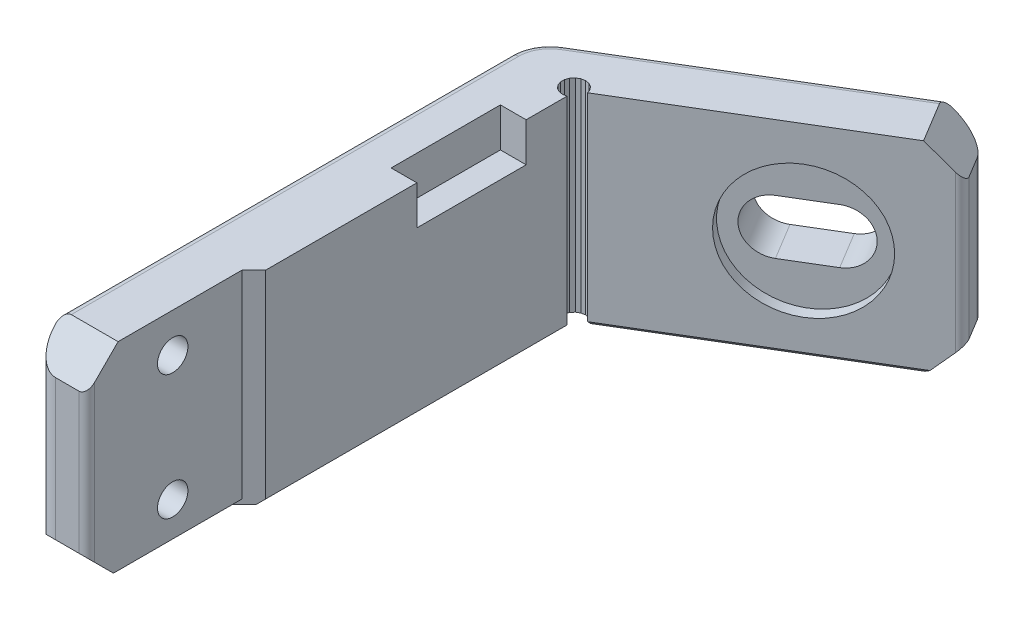
SolidWorks part; units mm, degrees
ref_plane "Front Plane" through (0, 0, 0) normal (0, 0, 1) x (1, 0, 0)
ref_plane "Top Plane" through (0, 0, 0) normal (0, 1, 0) x (1, 0, 0)
ref_plane "Right Plane" through (0, 0, 0) normal (1, 0, 0) x (0, 0, -1)
ref_plane "PY -20.700" through (0, -20.7, 0) normal (0, 1, 0) x (1, 0, 0)
sketch "leg and pad sketch" plane through (0, -20.7, 0) normal (0, 1, 0) x (1, 0, 0)
  line L0 (0.5513, 30.3327) -> (0.3673, 30.8194)
  line L1 (0.3673, 30.8194) -> (0.028, 31.2139)
  line L2 (0.028, 31.2139) -> (-0.4256, 31.4688)
  line L3 (-0.4256, 31.4688) -> (-0.939, 31.5534)
  line L4 (-0.939, 31.5534) -> (-1.4504, 31.4576)
  line L5 (-1.4504, 31.4576) -> (-1.8983, 31.1928)
  line L6 (-1.8983, 31.1928) -> (-2.2288, 30.7909)
  line L7 (-2.2288, 30.7909) -> (-2.4021, 30.3003)
  line L8 (-2.4021, 30.3003) -> (-2.3973, 29.78)
  line L9 (-2.3973, 29.78) -> (-2.2152, 29.2926)
  line L10 (-2.2152, 29.2926) -> (-1.8775, 28.8968)
  line L11 (-1.8775, 28.8968) -> (-1.4248, 28.6402)
  line L12 (-1.4248, 28.6402) -> (-0.9118, 28.5536)
  line L13 (-0.9118, 28.5536) -> (-0.4, 28.6475)
  line L14 (-0.4, 28.6475) -> (-0.4, -9.98)
  line L15 (-0.4, -9.98) -> (-1.92, -11.5)
  line L16 (-1.92, -11.5) -> (-1.92, -31.37)
  line L17 (-1.92, -31.37) -> (-8.92, -31.37)
  line L18 (-8.92, -31.37) -> (-8.92, 32.7926)
  line L19 (-8.92, 32.7926) -> (27.2048, 54.5947)
  line L20 (27.2048, 54.5947) -> (30.8218, 48.6015)
  line L21 (30.8218, 48.6015) -> (0.5513, 30.3327)
extrude "leg and pad" add sketch "leg and pad sketch" along normal mid plane 26
ref_plane "PX -1.350" through (-1.35, 0, 0) normal (1, 0, 0) x (0, 0, -1)
sketch "screw head relief sketch" plane through (-1.35, 0, 0) normal (1, 0, 0) x (0, 0, -1)
  line L0 (23.4, -12.7) -> (23.4, -6.7)
  line L1 (23.4, -6.7) -> (9.4, -6.7)
  line L2 (9.4, -6.7) -> (9.4, -12.7)
  line L3 (9.4, -12.7) -> (23.4, -12.7)
extrude "screw head relief" cut sketch "screw head relief sketch" against normal mid plane 4.7
sketch "insert flange relief sketch" plane through (0, -20.7, 0) normal (0, 1, 0) x (1, 0, 0)
  line L0 (18.3249, 39.8914) -> (17.0331, 42.0318)
  line L1 (17.0331, 42.0318) -> (9.7557, 37.6398)
  line L2 (9.7557, 37.6398) -> (11.0475, 35.4994)
  line L3 (11.0475, 35.4994) -> (18.3249, 39.8914)
revolve "insert flange relief" cut sketch "insert flange relief sketch" angle 360 about L0
sketch "M6 slot end 1 sketch" plane through (0, -20.7, 0) normal (0, 1, 0) x (1, 0, 0)
  line L0 (20.8933, 41.4415) -> (16.243, 49.147)
  line L1 (16.243, 49.147) -> (13.2464, 47.3385)
  line L2 (13.2464, 47.3385) -> (17.8968, 39.633)
  line L3 (17.8968, 39.633) -> (20.8933, 41.4415)
revolve "M6 slot end 1" cut sketch "M6 slot end 1 sketch" angle 360 about L0
sketch "M6 slot end 2 sketch" plane through (0, -20.7, 0) normal (0, 1, 0) x (1, 0, 0)
  line L0 (15.7564, 38.3413) -> (11.106, 46.0467)
  line L1 (11.106, 46.0467) -> (8.1094, 44.2382)
  line L2 (8.1094, 44.2382) -> (12.7598, 36.5328)
  line L3 (12.7598, 36.5328) -> (15.7564, 38.3413)
revolve "M6 slot end 2" cut sketch "M6 slot end 2 sketch" angle 360 about L0
sketch "M6 slot middle sketch" plane through (0, -20.7, 0) normal (0, 1, 0) x (1, 0, 0)
  line L0 (15.7564, 38.3413) -> (20.8933, 41.4415)
  line L1 (20.8933, 41.4415) -> (16.243, 49.147)
  line L2 (16.243, 49.147) -> (11.106, 46.0467)
  line L3 (11.106, 46.0467) -> (15.7564, 38.3413)
extrude "M6 slot middle" cut sketch "M6 slot middle sketch" against normal mid plane 7
ref_plane "PX -5.420" through (-5.42, 0, 0) normal (1, 0, 0) x (0, 0, -1)
sketch "screw holes sketch" plane through (-5.42, 0, 0) normal (1, 0, 0) x (0, 0, -1)
  circle A0 centre (-20.375, -28.7) radius 1.95
  circle A1 centre (-20.375, -12.7) radius 1.95
extrude "screw holes" cut sketch "screw holes sketch" against normal mid plane 9
chamfer "leg top corners" distance 4 angle 45 2 edges at (-5.42, -7.7, 31.37) (-5.42, -33.7, 31.37) tangent propagation no
chamfer "pad end corners" distance 4 angle 45 2 edges at (29.0133, -7.7, -51.5981) (29.0133, -33.7, -51.5981) tangent propagation no
fillet "outside of the bend" radius 5 1 edges at (-8.92, -20.7, -32.7926) tangent propagation no
fillet "leg top outer edge" radius 3 1 edges at (-8.92, -20.7, 31.37) tangent propagation no
fillet "pad end outer edge" radius 3 1 edges at (27.2048, -20.7, -54.5947) tangent propagation no
fillet "leg top inner edge" radius 1 1 edges at (-1.92, -20.7, 31.37) tangent propagation no
fillet "pad end inner edge" radius 1 1 edges at (30.8218, -20.7, -48.6015) tangent propagation no
chamfer "bed face chamfer" distance 0.6 angle 45 6 edges at (13.9742, -33.7, -38.4337) (8.6383, -33.7, -43.3894) (-1.92, -33.7, 19.435) (-0.4, -33.7, -9.3337) (-8.2742, -33.7, -32.4281) (-8.92, -33.7, -1.3001)
fillet "top face edge" radius 1 3 edges at (8.6383, -7.7, -43.3894) (-8.2742, -7.7, -32.4281) (-8.92, -7.7, -1.3001)
equation "\"diffL\" = 608.8mm"
equation "\"diffW\" = 329.4mm"
equation "\"diffT\" = 2.9mm"
equation "\"chanSlotW\" = 12.9mm"
equation "\"chanSlotDepth\" = 11.13mm"
equation "\"chanFloor\" = 1.57mm"
equation "\"chanLeg\" = 12.7mm"
equation "\"lightL\" = 605mm"
equation "\"lightW\" = 331mm"
equation "\"lightH\" = 92mm"
equation "\"lightSideFlat\" = 30mm"
equation "\"lightSlopeLen\" = 33.1mm"
equation "\"lightWingDepth\" = 47.9mm"
equation "\"lightWingFlat\" = 90.2mm"
equation "\"lightChanW\" = 99.6mm"
equation "\"lightChanStand\" = 44.1mm"
equation "\"insFlangeD\" = 12.3mm"
equation "\"insFromEnd\" = 20.7mm"
equation "\"insUpSlope\" = 20.8mm"
equation "\"gaugeH\" = 10mm"
equation "\"gaugeStepLen\" = 14mm"
equation "\"gaugeStepW0\" = 13.1mm"
equation "\"gaugeStepDW\" = 0.2mm"
equation "\"gaugeSteps\" = 5mm"
equation "\"gaugeHandleLen\" = 30mm"
equation "\"gaugeHandleW\" = 24mm"
equation "\"gaugeSlot0\" = 3mm"
equation "\"gaugeSlotD\" = 0.1mm"
equation "\"gaugeSlotDepth\" = 8mm"
equation "\"gap\" = 25.4mm"
equation "\"edgeL\" = 1mm"
equation "\"edgeW\" = 0.75mm"
equation "\"proud\" = 1.5mm"
equation "\"seatClr\" = 0.15mm"
equation "\"tongueClrZ\" = 0.1mm"
equation "\"tongueClrX\" = 0.25mm"
equation "\"tongueLen\" = 30mm"
equation "\"armSide\" = 45mm"
equation "\"armEnd\" = 20mm"
equation "\"cornerCham\" = 3mm"
equation "\"brkW\" = 26mm"
equation "\"brkT\" = 7mm"
equation "\"brkSeatClr\" = 0.2mm"
equation "\"brkScrewSpan\" = 16mm"
equation "\"pilotD\" = 2.7mm"
equation "\"pilotDepth\" = 10mm"
equation "\"screwClrD\" = 3.9mm"
equation "\"jogBelow\" = 4mm"
equation "\"padT\" = 7mm"
equation "\"padLen\" = 31mm"
equation "\"m6Clr\" = 7mm"
equation "\"m6Slot\" = 3mm"
equation "\"flangeRelD\" = 17mm"
equation "\"flangeRelDepth\" = 1.5mm"
equation "\"relLen\" = 7mm"
equation "\"relDepth\" = 4mm"
equation "\"relLand\" = 2mm"
equation "\"knockN\" = 100mm"
equation "\"petgcfE\" = 3000mm"
equation "\"mockExtent\" = 110mm"
equation "\"relZnear\" = 9.4mm"
equation "\"relZfar\" = 23.4mm"
equation "\"headD\" = 8mm"
equation "\"headH\" = 2.5mm"
equation "\"headFromEnd\" = 6.8mm"
equation "\"headBack\" = 16.4mm"
equation "\"sideClr\" = 0.4mm"
equation "\"cornerRelR\" = 1.5mm"
equation "\"cornerRelBack\" = 0.6mm"
equation "\"endHeadH\" = 2.8mm"
equation "\"footClr\" = 1.2mm"
equation "\"footEndClr\" = 3.5mm"
equation "\"footLift\" = 6mm"
equation "\"footBlockClr\" = 0.5mm"
equation "\"footBack\" = 50mm"
equation "\"footFwd\" = 10mm"
equation "\"footBraceEnd\" = 3mm"
equation "\"footLoadN\" = 25mm"
equation "\"spacerLen\" = 60mm"
equation "\"spacerShort\" = 0.5mm"
equation "\"spacerCham\" = 0.8mm"
equation "\"spacerPerSide\" = 3mm"
equation "\"spacerPerEnd\" = 1mm"
equation "\"toolR\" = 9mm"
equation "\"visR\" = 4mm"
equation "\"edgeR\" = 1mm"
equation "\"bendOutR\" = 5mm"
equation "\"insideR\" = 2.5mm"
equation "\"footCornerR\" = 10mm"
equation "\"footFrontR\" = 8mm"
equation "\"braceKinkR\" = 12mm"
equation "\"bedCham\" = 1mm"
equation "\"bedChamSmall\" = 0.6mm"
equation "\"soleTopR\" = 2mm"
